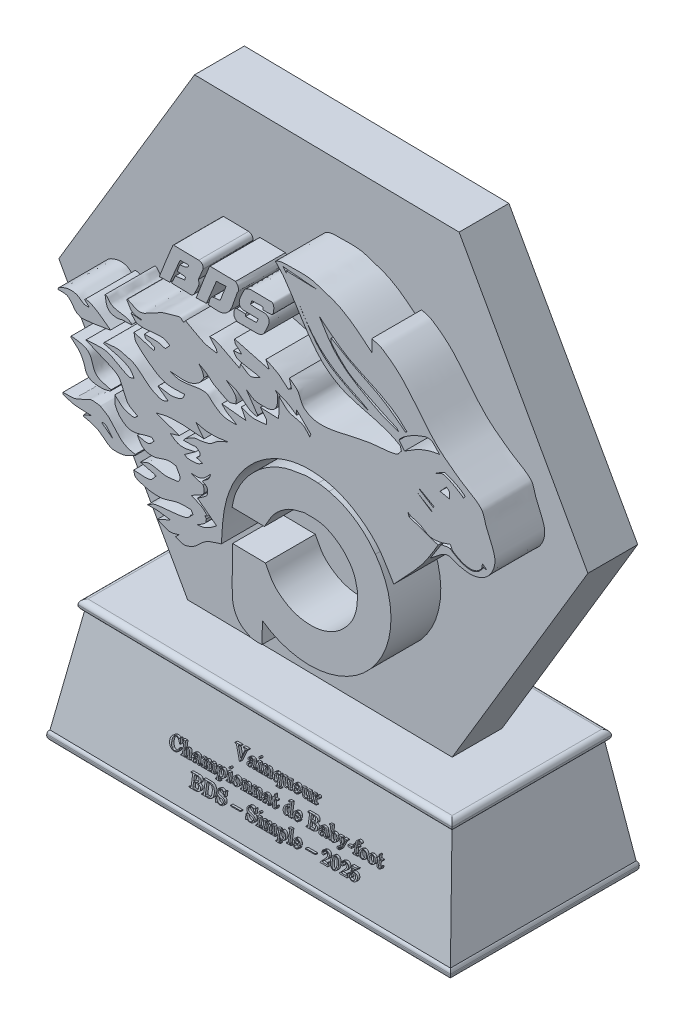
SolidWorks part; units mm, degrees
ref_plane "Plan de face" through (0, 0, 0) normal (0, 0, 1) x (1, 0, 0)
ref_plane "Plan de dessus" through (0, 0, 0) normal (0, 1, 0) x (1, 0, 0)
ref_plane "Plan de droite" through (0, 0, 0) normal (1, 0, 0) x (0, 0, -1)
sketch "Esquisse3" plane through (0, 0, 0) normal (0, 0, 1) x (1, 0, 0)
  line L0 (336.1667, 1024) -> (1680.8333, 1024) construction
  line L1 (1302, 1687) -> (1302, 1736)
  line L2 (1537, 1090) -> (1581, 1159)
  line L3 (1445.599, 1206.4377) -> (1452, 1191)
  line L4 (1452, 1191) -> (1568, 1151)
  line L5 (514, 653) -> (528, 667)
  line L6 (441, 677) -> (494, 701)
  line L7 (584, 764) -> (577, 778)
  line L8 (437, 826) -> (373, 842)
  line L9 (484, 1110) -> (443, 1141)
  line L10 (347, 1280) -> (428, 1256)
  line L11 (428, 1256) -> (430, 1269)
  line L12 (473, 1286) -> (491, 1306)
  line L13 (335, 1341) -> (376, 1337)
  line L14 (376, 1337) -> (378, 1339)
  line L15 (318, 1380) -> (321, 1382)
  line L16 (546, 1414) -> (554, 1424)
  line L17 (771, 1367) -> (775, 1384)
  line L18 (746, 1416) -> (780, 1420)
  line L19 (751, 1459) -> (890, 1422)
  line L20 (890, 1422) -> (877, 1451)
  line L21 (967, 1392) -> (980, 1399)
  line L22 (980, 1399) -> (971, 1433)
  line L23 (945, 1808) -> (1083, 1796)
  line L24 (1083, 1796) -> (959, 1800)
  line L25 (959, 1800) -> (958, 1794)
  line L26 (958, 1794) -> (960, 1791)
  line L27 (960, 1791) -> (945, 1808)
  line L28 (1444, 1481) -> (1437, 1478)
  line L29 (1433, 1410) -> (1411, 1437)
  line L30 (1677, 1373) -> (1670, 1365)
  line L31 (1613, 1334) -> (1576, 1342)
  line L32 (1601, 1369) -> (1576, 1342)
  line L33 (1000, 1318) -> (999, 1338)
  line L34 (999, 1338) -> (1057, 1281)
  line L35 (1057, 1281) -> (1053, 1269)
  line L36 (930, 1348) -> (928, 1270)
  line L37 (928, 1270) -> (855, 1273)
  line L38 (778, 1236) -> (797, 1198)
  line L39 (840, 1234) -> (844, 1240)
  line L40 (844, 1240) -> (799, 1306)
  line L41 (1654, 1326) -> (1658, 1324)
  line L42 (1658, 1324) -> (1654, 1325)
  line L43 (1654, 1326) -> (1654, 1325)
  line L44 (1551, 1277) -> (1494, 1309)
  line L45 (1551, 1277) -> (1549, 1272)
  line L46 (1549, 1272) -> (1493, 1307)
  line L47 (1493, 1307) -> (1494, 1309)
  line L48 (1483, 1293) -> (1544, 1256)
  line L49 (1542, 1254) -> (1544, 1256)
  line L50 (1542, 1254) -> (1483, 1293)
  line L51 (1746, 1175) -> (1763, 1163)
  line L52 (1763, 1163) -> (1760, 1162)
  line L53 (1760, 1162) -> (1750.0098, 1163.665)
  line L55 (1743, 1157) -> (1746, 1175)
  line L56 (598, 970) -> (623, 963)
  line L57 (550, 957) -> (594, 988)
  line L58 (493, 1001) -> (529, 1012)
  line L59 (529, 1012) -> (437, 1044)
  line L60 (595, 1092) -> (628, 1050)
  line L61 (602, 831) -> (679, 773)
  line L62 (638, 777) -> (631, 785)
  line L63 (631, 785) -> (643, 789)
  line L64 (574, 905) -> (625, 888)
  line L65 (232, 1354) -> (231, 1353)
  line L66 (168, 1277) -> (149, 1295)
  line L67 (153, 1299) -> (149, 1295)
  line L68 (255, 1034) -> (253, 1029)
  line L69 (95, 1141) -> (94, 1136)
  line L70 (352, 858) -> (352, 854)
  line L71 (144, 891) -> (144, 887)
  line L72 (144, 891) -> (174, 905)
  line L73 (62, 923) -> (62, 929)
  line L74 (1234, 1501) -> (1241.5869, 1497.8498)
  line L75 (678, 1623) -> (717, 1625)
  line L76 (862.8036, 535.7693) -> (861, 451)
  line L77 (743, 744) -> (875, 742)
  line L78 (871, 867) -> (741, 869)
  line L79 (865, 1617) -> (864, 1628)
  line L80 (821, 1627) -> (864, 1628)
  line L81 (821, 1627) -> (814, 1611)
  line L82 (794, 1568) -> (795, 1559)
  line L83 (795, 1559) -> (839, 1560)
  line L84 (839, 1560) -> (846, 1576)
  line L85 (693, 1564) -> (717, 1625)
  line L86 (700, 1208) -> (797, 1198)
  line L87 (678, 1623) -> (638, 1526)
  line L88 (638, 1526) -> (597, 1525)
  line L89 (498, 1527) -> (513, 1559)
  line L90 (513, 1559) -> (551, 1564)
  line L91 (551, 1564) -> (554, 1576)
  line L92 (554, 1576) -> (521, 1580)
  line L93 (521, 1580) -> (531, 1607)
  line L94 (567, 1620) -> (565, 1624)
  line L95 (565, 1624) -> (532, 1623)
  line L96 (532, 1623) -> (491, 1526)
  line L97 (491, 1526) -> (449, 1525)
  line L98 (624.8796, 1638.9367) -> (605.4226, 1592.9044)
  line L99 (604.6984, 1566.7534) -> (589.7477, 1536.2154)
  line L100 (573.9653, 1525) -> (498, 1527)
  line L101 (264.0246, 866.4916) -> (217, 902)
  arc A0 (607, 1661) -> (624.8796, 1638.9367) centre (606.6207, 1642.4164) cw
  arc A1 (605.4226, 1592.9044) -> (604.6984, 1566.7534) centre (576.3678, 1580.6235) cw
  arc A2 (589.7477, 1536.2154) -> (573.9653, 1525) centre (571.5353, 1545.1319) cw
  arc A3 (862.8036, 535.7693) -> (1316.5669, 993.1753) centre (1052.5129, 801.3486) ccw
  arc A4 (1129.8066, 1118.4411) -> (1086.8314, 1125.9164) centre (1052.5129, 801.3486) ccw
  spline S0 degree 3 poles (915, 1811) (920.6667, 1813.6667) (925.9164, 1817.5129) (932, 1819) (941.1183, 1821.2289) (950.6154, 1822.1997) (960, 1822) (1000.4122, 1821.1402) (1042.9169, 1827.5488) (1081, 1814) (1113.09, 1802.5833) (1146.9207, 1794.9796) (1177, 1779) (1222.6884, 1754.728) (1262.8151, 1720.7801) (1302, 1687) knots 0 0 0 0 1 1 1 2 2 2 3 3 3 4 4 4 5 5 5 5
  spline S1 degree 3 poles (1302, 1736) (1317, 1730.3333) (1333.5756, 1727.7691) (1347, 1719) (1375.3732, 1700.4659) (1402.4901, 1679.4098) (1426, 1655) (1472.4253, 1606.7976) (1509.2053, 1549.8439) (1556, 1502) (1583.8463, 1473.5293) (1617.0572, 1450.7835) (1649, 1427) (1678.4402, 1405.0798) (1714.1626, 1391.0701) (1740, 1365) (1752.6359, 1352.2503) (1753.5167, 1331.7388) (1760, 1315) (1771.8506, 1284.4039) (1788.3447, 1255.1289) (1795, 1223) (1798.2706, 1207.2107) (1795.1053, 1189.924) (1789, 1175) (1782.6895, 1159.5742) (1772.3333, 1145) (1759, 1135) (1744.6396, 1124.2297) (1726.7988, 1117.3288) (1709, 1115) (1690.0565, 1112.5214) (1670.8107, 1117.6598) (1652, 1121) (1635.0445, 1124.0108) (1618.6273, 1138.4821) (1602, 1134) (1576.7377, 1127.1902) (1558.6667, 1104.6667) (1537, 1090) knots 0 0 0 0 1 1 1 2 2 2 3 3 3 4 4 4 5 5 5 6 6 6 7 7 7 8 8 8 9 9 9 10 10 10 11 11 11 12 12 12 13 13 13 13
  spline S2 degree 3 poles (1581, 1159) (1592.9734, 1159.921) (1605.2835, 1164.5242) (1617, 1162.6354) knots 0 0 0 0 0.921032 0.921032 0.921032 0.921032
  spline S3 degree 3 poles (1626.6587, 1159.5467) (1622.8097, 1165.1023) (1620.6123, 1172.2204) (1617, 1178) knots 2.277549 2.277549 2.277549 2.277549 3 3 3 3
  spline S4 degree 3 poles (1617, 1178) (1603, 1173.6667) (1589.4463, 1167.4664) (1575, 1165) (1561.8527, 1162.7553) (1547.9107, 1160.6528) (1535, 1164) (1519.9865, 1167.8924) (1508.1253, 1179.5944) (1494, 1186) (1479.3968, 1192.6224) (1461.6455, 1193.1408) (1449, 1203) (1447.7012, 1204.0126) (1446.5813, 1205.1696) (1445.599, 1206.4377) knots 0 0 0 0 1 1 1 2 2 2 3 3 3 4 4 4 4.153424 4.153424 4.153424 4.153424
  spline S5 degree 3 poles (1568, 1151) (1562.6667, 1142) (1557.7044, 1132.7695) (1552, 1124) (1535.3644, 1098.4259) (1520.3192, 1071.6124) (1501, 1048) (1466.1847, 1005.448) (1427, 966.6667) (1390, 926) knots 0 0 0 0 1 1 1 2 2 2 3 3 3 3
  spline S6 degree 3 poles (1390, 926) (1370, 957.3333) (1353.6926, 991.3567) (1330, 1020) (1308.6483, 1045.8133) (1283.3166, 1068.6086) (1256, 1088) (1228.8829, 1107.2498) (1199.2278, 1123.5669) (1168, 1135) (1137.6118, 1146.1257) (1105.2971, 1152.9709) (1073, 1155) (1040.9523, 1157.0135) (1008.2798, 1154.2583) (977, 1147) (947.2739, 1140.1022) (918.485, 1128.1581) (892, 1113) (864.9769, 1097.534) (839.9344, 1078.0981) (818, 1056) (794.8916, 1032.7191) (774.5075, 1006.3461) (758, 978) (741.238, 949.2167) (728.0873, 918.0447) (719, 886) (703.7834, 832.3415) (700.9314, 775.6973) (698, 720) knots 0 0 0 0 1 1 1 2 2 2 3 3 3 4 4 4 5 5 5 6 6 6 7 7 7 8 8 8 9 9 9 10 10 10 10
  spline S7 degree 3 poles (698, 720) (678, 712.6667) (656.4567, 708.6361) (638, 698) (616.6203, 685.6795) (602.0285, 663.1191) (580, 652) (548.5317, 636.116) (537.3019, 642.1258) (514, 653) knots 0 0 0 0 1 1 1 2 2 2 3 3 3 3
  spline S8 degree 3 poles (528, 667) (525.4489, 666.4898) (497.27, 654.9179) (484, 660) (469.6066, 665.5124) (455.3333, 671.3333) (441, 677) knots 0 0 0 0 1 1 1 2 2 2 2
  spline S9 degree 3 poles (494, 701) (477, 703.3333) (460.1099, 706.6982) (443, 708) (429.3727, 709.0369) (415.6667, 708) (402, 708) knots 0 0 0 0 1 1 1 2 2 2 2
  spline S10 degree 3 poles (402, 708) (412, 713.3333) (420.9098, 721.6652) (432, 724) (472.1351, 732.4495) (514.3355, 729.562) (554, 740) (566.3846, 743.2591) (574, 756) (584, 764) knots 0 0 0 0 1 1 1 2 2 2 3 3 3 3
  spline S11 degree 3 poles (577, 778) (560, 777.6667) (542.804, 779.5957) (526, 777) (501.5513, 773.2234) (478.6767, 760.7501) (454, 759) (430.9039, 757.362) (407.166, 760.3084) (385, 767) (348.0895, 778.1428) (350.2029, 779.9856) (346, 801) knots 0 0 0 0 1 1 1 2 2 2 3 3 3 4 4 4 4
  spline S12 degree 3 poles (346, 801) (367.6667, 801) (390.1074, 795.2603) (411, 801) (422.5936, 804.185) (428.3333, 817.6667) (437, 826) knots 0 0 0 0 1 1 1 2 2 2 2
  spline S13 degree 3 poles (373, 842) (385, 846.3333) (396.25, 854.5364) (409, 855) (435.1955, 855.9526) (460.8999, 842.5721) (487, 845) (500.0501, 846.214) (513, 848.3333) (526, 850) knots 0 0 0 0 1 1 1 2 2 2 3 3 3 3
  spline S14 degree 3 poles (526, 850) (528, 856.3333) (533.3025, 862.4874) (532, 869) (529.7195, 880.4027) (521.3333, 889.6667) (516, 900) knots 0 0 0 0 1 1 1 2 2 2 2
  spline S15 degree 3 poles (516, 900) (505.3333, 901) (494.6103, 904.4832) (484, 903) (463.1813, 900.0899) (443.9834, 888.259) (423, 887) (409.6035, 886.1962) (395.1111, 889.4731) (384, 897) (373.1244, 904.3673) (368.6667, 918.3333) (361, 929) knots 0 0 0 0 1 1 1 2 2 2 3 3 3 4 4 4 4
  spline S16 degree 3 poles (361, 929) (376, 927) (391.1443, 920.1176) (406, 923) (415.5122, 924.8457) (420.6667, 935.6667) (428, 942) knots 0 0 0 0 1 1 1 2 2 2 2
  spline S17 degree 3 poles (428, 942) (424, 944.6667) (420.7819, 950.4947) (416, 950) (390.5019, 947.3623) (366.6332, 933.2229) (341, 933) (326.6401, 932.8751) (312.2458, 940.0695) (301, 949) (288.6786, 958.7846) (279.0102, 972.4593) (273, 987) (268.2733, 998.4355) (271, 1011.6667) (270, 1024) knots 0 0 0 0 1 1 1 2 2 2 3 3 3 4 4 4 5 5 5 5
  spline S18 degree 3 poles (270, 1024) (283.6667, 1013.6667) (294.8981, 998.8552) (311, 993) (347.6119, 979.6866) (348.3963, 982.3963) (362, 996) knots 0 0 0 0 1 1 1 2 2 2 2
  spline S19 degree 3 poles (362, 996) (349.3333, 1004) (334.0691, 1008.9069) (324, 1020) (313.6798, 1031.3697) (310.3408, 1047.5133) (303, 1061) (296.0028, 1073.8554) (292.6952, 1090.1997) (281, 1099) (257.6507, 1116.5698) (228.5806, 1124.8608) (202, 1137) (186.2331, 1144.2006) (170, 1150.3333) (154, 1157) knots 0 0 0 0 1 1 1 2 2 2 3 3 3 4 4 4 5 5 5 5
  spline S20 degree 3 poles (154, 1157) (155.3333, 1157.3333) (156.6257, 1157.9838) (158, 1158) (184.9981, 1158.3176) (212.8154, 1164.5853) (239, 1158) (269.9392, 1150.2189) (294.8755, 1126.5021) (325, 1116) (332.348, 1113.4383) (340.3333, 1118.6667) (348, 1120) knots 0 0 0 0 1 1 1 2 2 2 3 3 3 4 4 4 4
  spline S21 degree 3 poles (348, 1120) (341.6667, 1128.6667) (337.8909, 1139.9855) (329, 1146) (298.4419, 1166.6716) (259.637, 1171.4544) (224, 1181) knots 0 0 0 0 1 1 1 2 2 2 2
  spline S22 degree 3 poles (224, 1181) (226, 1182.6667) (227.4051, 1185.7896) (230, 1186) (253.9215, 1187.9396) (279.1881, 1193.4577) (302, 1186) (318.0306, 1180.7592) (335.4753, 1178.5719) (350, 1170) (376.6403, 1154.2779) (396.4202, 1128.0088) (424, 1114) (459.6438, 1095.8952) (463.5958, 1099.7979) (484, 1110) knots 0 0 0 0 1 1 1 2 2 2 3 3 3 4 4 4 5 5 5 5
  spline S23 degree 3 poles (443, 1141) (448.6949, 1142.8983) (443.1637, 1141.6511) (450, 1141) (469.6483, 1139.1287) (489.5876, 1132.4345) (509, 1136) (542.4065, 1142.1359) (543.3635, 1148.1815) (551, 1166) knots 0 0 0 0 1 1 1 2 2 2 3 3 3 3
  spline S24 degree 3 poles (551, 1166) (526.3333, 1166.3333) (501.1599, 1162.0146) (477, 1167) (458.1643, 1170.8867) (440.8598, 1181.1209) (425, 1192) (400.2227, 1208.996) (375.9299, 1227.515) (356, 1250) (349.0749, 1257.813) (350, 1270) (347, 1280) knots 0 0 0 0 1 1 1 2 2 2 3 3 3 4 4 4 4
  spline S25 degree 3 poles (430, 1269) (388.8184, 1289.0628) (394.9727, 1274.0957) (389, 1295) knots 0 0 0 0 1 1 1 1
  spline S26 degree 3 poles (389, 1295) (407, 1294.6667) (425.0994, 1295.9179) (443, 1294) (453.2906, 1292.8974) (463, 1288.6667) (473, 1286) knots 0 0 0 0 1 1 1 2 2 2 2
  spline S27 degree 3 poles (491, 1306) (482, 1310.3333) (473.9581, 1318.2159) (464, 1319) (430.7546, 1321.6178) (396.8737, 1310.3936) (364, 1316) (351.4189, 1318.1456) (344.6667, 1332.6667) (335, 1341) knots 0 0 0 0 1 1 1 2 2 2 3 3 3 3
  spline S28 degree 3 poles (378, 1339) (365.6667, 1341.6667) (351.4183, 1339.8809) (341, 1347) (329.9297, 1354.5647) (325.6667, 1369) (318, 1380) knots 0 0 0 0 1 1 1 2 2 2 2
  spline S29 degree 3 poles (321, 1382) (337.6667, 1375.6667) (353.1715, 1362.8181) (371, 1363) (388.3324, 1363.1769) (403.2308, 1375.8044) (419, 1383) (437.5803, 1391.4784) (454.2051, 1404.9727) (474, 1410) (535.009, 1425.4944) (528.4316, 1431.5684) (546, 1414) knots 0 0 0 0 1 1 1 2 2 2 3 3 3 4 4 4 4
  spline S30 degree 3 poles (554, 1424) (579.3333, 1410.6667) (603.3907, 1394.5593) (630, 1384) (645.7983, 1377.7308) (663.3333, 1377.3333) (680, 1374) knots 0 0 0 0 1 1 1 2 2 2 2
  spline S31 degree 3 poles (680, 1374) (679.3333, 1378) (680.2674, 1382.638) (678, 1386) (670.338, 1397.3609) (660, 1406.6667) (651, 1417) knots 0 0 0 0 1 1 1 2 2 2 2
  spline S32 degree 3 poles (651, 1417) (660, 1416) (669.6412, 1417.4828) (678, 1414) (710.0621, 1400.6408) (740, 1382.6667) (771, 1367) knots 0 0 0 0 1 1 1 2 2 2 2
  spline S33 degree 3 poles (775, 1384) (791.3079, 1376.2006) (808.3586, 1355.94) (825, 1363) (834.7522, 1367.1373) (844.3333, 1371.6667) (854, 1376) knots 0 0 0 0 1 1 1 2 2 2 2
  spline S34 degree 3 poles (854, 1376) (846, 1378) (838.054, 1380.2299) (830, 1382) (807.7162, 1386.8975) (784.1489, 1387.4397) (763, 1396) (754.8896, 1399.2828) (751.6667, 1409.3333) (746, 1416) knots 0 0 0 0 1 1 1 2 2 2 3 3 3 3
  spline S35 degree 3 poles (780, 1420) (749.6731, 1451.41) (753.337, 1435.6296) (751, 1459) knots 0 0 0 0 1 1 1 1
  spline S36 degree 3 poles (877, 1451) (893.6667, 1442.3333) (911.2896, 1435.2991) (927, 1425) (941.4558, 1415.5234) (953.6667, 1403) (967, 1392) knots 0 0 0 0 1 1 1 2 2 2 2
  spline S37 degree 3 poles (971, 1433) (982, 1424) (995.2325, 1417.1862) (1004, 1406) (1014.9466, 1392.0336) (1015.9477, 1371.0219) (1029, 1359) (1042.717, 1346.3659) (1061.5274, 1338.5577) (1080, 1336) (1108.8188, 1332.0097) (1138.5521, 1336.904) (1167, 1343) (1206.3139, 1351.4244) (1245.3733, 1361.1971) (1285, 1368) (1323.1007, 1374.5409) (1362.6291, 1373.1077) (1400, 1383) (1409.5699, 1385.5332) (1414, 1397) (1421, 1404) knots 0 0 0 0 1 1 1 2 2 2 3 3 3 4 4 4 5 5 5 6 6 6 7 7 7 7
  spline S38 degree 3 poles (1421, 1404) (1418.3333, 1410) (1418.5514, 1418.4939) (1413, 1422) (1392.0534, 1435.2294) (1368.4815, 1444.1007) (1345, 1452) (1296.0045, 1468.4823) (1244.0544, 1475.9476) (1196, 1495) (1167.7816, 1506.1879) (1141.5168, 1522.8061) (1118, 1542) (1095.6955, 1560.2044) (1076.9818, 1582.7512) (1060, 1606) (1020.8468, 1659.6027) (988.3318, 1717.8068) (950, 1772) (939.9132, 1786.2607) (926.6667, 1798) (915, 1811) knots 0 0 0 0 1 1 1 2 2 2 3 3 3 4 4 4 5 5 5 6 6 6 7 7 7 7
  spline S39 degree 3 poles (1234, 1501) (1233.3071, 1501.2746) (1232.6555, 1501.6452) (1232, 1502) (1204.3218, 1516.9788) (1175.736, 1530.3978) (1149, 1547) (1118.5402, 1565.9145) (1091.9951, 1591.6844) (1070, 1620) (1033.5835, 1666.8811) (1004.352, 1718.9828) (974, 1770) knots 5 5 5 5 6 6 6 7 7 7 8 8 8 9 9 9 9
  spline S40 degree 3 poles (974, 1770) (1009.2632, 1712.8836) (1040.7926, 1651.7205) (1088, 1604) (1103.129, 1588.7065) (1119.6469, 1574.7141) (1137, 1562) (1153.4175, 1549.9713) (1171.1465, 1539.7712) (1189, 1530) (1220.5161, 1512.7513) (1254.8005, 1500.4619) (1285, 1481) (1298.4541, 1472.3296) (1262.1817, 1489.0571) (1241.5869, 1497.8498) knots 0 0 0 0 1 1 1 2 2 2 3 3 3 4 4 4 4.876532 4.876532 4.876532 4.876532
  spline S41 degree 3 poles (1091, 1708) (1133.0564, 1673.7942) (1174.7177, 1637.6494) (1223, 1613) (1284.8912, 1581.4029) (1352.3155, 1557.8776) (1407, 1515) (1420.1811, 1504.6649) (1431.6667, 1492.3333) (1444, 1481) knots 0 0 0 0 1 1 1 2 2 2 3 3 3 3
  spline S42 degree 3 poles (1437, 1478) (1402.4117, 1505.2291) (1367.5024, 1532.6613) (1329, 1554) (1294.7083, 1573.005) (1258.5431, 1588.4558) (1224, 1607) (1195.1856, 1622.4688) (1167.3333, 1639.6667) (1139, 1656) knots 0 0 0 0 1 1 1 2 2 2 3 3 3 3
  spline S43 degree 3 poles (1139, 1656) (1139.3333, 1650.6667) (1136.7754, 1644.2611) (1140, 1640) (1156.078, 1618.7541) (1175.1654, 1599.7898) (1195, 1582) (1207.6652, 1570.6405) (1221.9981, 1561.0243) (1237, 1553) (1279.4612, 1530.2882) (1323.6737, 1511.0145) (1367, 1490) (1406.2609, 1470.9573) (1395.2349, 1482.5182) (1409, 1466) knots 0 0 0 0 1 1 1 2 2 2 3 3 3 4 4 4 5 5 5 5
  spline S44 degree 3 poles (1409, 1466) (1382.5166, 1475.5954) (1354.8689, 1482.7719) (1330, 1496) (1264.0429, 1531.0836) (1201.8033, 1560.9883) (1152, 1618) (1128.157, 1645.2939) (1110.3276, 1677.3424) (1091, 1708) knots 0 0 0 0 1 1 1 2 2 2 3 3 3 3
  spline S45 degree 3 poles (1411, 1437) (1422.7965, 1460.5929) (1479.2149, 1489.3274) (1503, 1497) (1509.6241, 1499.1368) (1516.0477, 1502.6689) (1523, 1503) (1528.3377, 1503.2542) (1533.6929, 1502.6244) (1539, 1502) (1546.2224, 1501.1503) (1568.8037, 1474.1963) (1574, 1469) knots 0 0 0 0 1 1 1 2 2 2 3 3 3 4 4 4 4
  spline S46 degree 3 poles (1574, 1469) (1515.6013, 1461.3828) (1480.7028, 1441.8019) (1433, 1410) knots 0 0 0 0 1 1 1 1
  spline S47 degree 3 poles (1556, 1394) (1558.3701, 1396.3701) (1590.3583, 1416) (1594, 1416) (1607.1855, 1416) (1667.2767, 1387.5849) (1677, 1373) knots 0 0 0 0 1 1 1 2 2 2 2
  spline S48 degree 3 poles (1670, 1365) (1657.2666, 1377.7334) (1604.6796, 1406.1748) (1589, 1407) (1577.874, 1407.5856) (1564.0025, 1397.8273) (1556, 1394) knots 0 0 0 0 1 1 1 2 2 2 2
  spline S49 degree 3 poles (1601, 1369) (1604.5506, 1366.1595) (1613.803, 1362.3203) (1614, 1357) (1614.284, 1349.3313) (1613.3333, 1341.6667) (1613, 1334) knots 0 0 0 0 1 1 1 2 2 2 2
  spline S50 degree 3 poles (914, 1363) (932, 1355.3333) (950.665, 1349.0706) (968, 1340) (979.4691, 1333.9987) (989.3333, 1325.3333) (1000, 1318) knots 0 0 0 0 1 1 1 2 2 2 2
  spline S51 degree 3 poles (1053, 1269) (1043.6667, 1278.3333) (1036.6084, 1290.7178) (1025, 1297) (1007.4766, 1306.4832) (985.5551, 1305.5757) (968, 1315) (953.219, 1322.9351) (942.6667, 1337) (930, 1348) knots 0 0 0 0 1 1 1 2 2 2 3 3 3 3
  spline S52 degree 3 poles (855, 1273) (882.3131, 1233.6692) (882.4018, 1251.411) (878, 1225) knots 0 0 0 0 1 1 1 1
  spline S53 degree 3 poles (878, 1225) (860.3333, 1223.6667) (842.6107, 1219.0628) (825, 1221) (808.6534, 1222.7981) (793.6667, 1231) (778, 1236) knots 0 0 0 0 1 1 1 2 2 2 2
  spline S54 degree 3 poles (700, 1208) (706.3333, 1201.6667) (711.7033, 1194.1943) (719, 1189) (731.5298, 1180.0804) (745.6667, 1173.6667) (759, 1166) knots 0 0 0 0 1 1 1 2 2 2 2
  spline S55 degree 3 poles (759, 1166) (757, 1165.3333) (755.1067, 1163.922) (753, 1164) (736.9555, 1164.5942) (720.3884, 1163.4201) (705, 1168) (691.6848, 1171.9629) (680.5843, 1181.3316) (669, 1189) (656.8812, 1197.0223) (648.4052, 1213.0732) (634, 1215) (592.68, 1220.5269) (547.8534, 1195.8903) (509, 1211) (503.981, 1212.9518) (499, 1215) (494, 1217) knots 0 0 0 0 1 1 1 2 2 2 3 3 3 4 4 4 5 5 5 6 6 6 6
  spline S56 degree 3 poles (494, 1217) (517.3333, 1216.3333) (540.9428, 1211.3594) (564, 1215) (579.9136, 1217.5127) (595.0147, 1225.4639) (608, 1235) (617.0274, 1241.6295) (621.3333, 1253) (628, 1262) knots 0 0 0 0 1 1 1 2 2 2 3 3 3 3
  spline S57 degree 3 poles (628, 1262) (625.6667, 1269.3333) (624.5116, 1277.1523) (621, 1284) (617.7448, 1290.3476) (612.3333, 1295.3333) (608, 1301) knots 0 0 0 0 1 1 1 2 2 2 2
  spline S58 degree 3 poles (608, 1301) (617.3333, 1295.6667) (627.138, 1291.0844) (636, 1285) (649.5212, 1275.7168) (660.3578, 1262.3895) (675, 1255) (734.878, 1224.7812) (723.0011, 1223.8575) (757, 1236) knots 0 0 0 0 1 1 1 2 2 2 3 3 3 3
  spline S59 degree 3 poles (757, 1236) (756.6667, 1244.3333) (759.5511, 1253.4538) (756, 1261) (748.0708, 1277.8495) (730.7925, 1288.6881) (716, 1300) knots 0 0 0 0 1 1 1 2 2 2 2
  spline S60 degree 3 poles (716, 1300) (730, 1294.6667) (745.1306, 1291.6696) (758, 1284) (778.4448, 1271.8157) (794.6796, 1253.3905) (815, 1241) (822.3886, 1236.4947) (831.6667, 1236.3333) (840, 1234) knots 0 0 0 0 1 1 1 2 2 2 3 3 3 3
  spline S61 degree 3 poles (799, 1306) (810.3333, 1299.3333) (820.288, 1289.3606) (833, 1286) (850.1072, 1281.4774) (868.3163, 1283.6316) (886, 1283) (887.0534, 1282.9624) (888.0572, 1283.5286) (889, 1284) (896.7345, 1287.8672) (906.3175, 1289.4818) (912, 1296) (918.3862, 1303.3254) (922.4031, 1313.3001) (923, 1323) (924.841, 1352.9155) (924.4477, 1352.5523) (914, 1363) knots 0 0 0 0 1 1 1 2 2 2 3 3 3 4 4 4 5 5 5 6 6 6 6
  spline S62 degree 3 poles (595, 1092) (609.6667, 1088.6667) (624.0211, 1083.3617) (639, 1082) (675.9728, 1078.6388) (692.3078, 1083.4907) (725, 1088) knots 0 0 0 0 1 1 1 2 2 2 2
  spline S63 degree 3 poles (725, 1088) (711.5274, 1081.2637) (696.9722, 1076.6557) (684, 1069) (673.3204, 1062.6973) (664.9736, 1052.7756) (654, 1047) (645.6935, 1042.6282) (636.1763, 1040.9764) (627, 1039) (602.8772, 1033.8043) (599.6204, 1038.6814) (587, 1032) (576.3252, 1026.3486) (565.0499, 1021.6999) (555, 1015) (550.8769, 1012.2513) (548.3333, 1007.6667) (545, 1004) knots 0 0 0 0 1 1 1 2 2 2 3 3 3 4 4 4 5 5 5 6 6 6 6
  spline S64 degree 3 poles (545, 1004) (600.4214, 1002.0889) (592.1008, 1015.5116) (613, 992) knots 0 0 0 0 1 1 1 1
  spline S65 degree 3 poles (613, 992) (612.3333, 988.6667) (612.915, 984.8086) (611, 982) (607.6779, 977.1275) (602.3333, 974) (598, 970) knots 0 0 0 0 1 1 1 2 2 2 2
  spline S66 degree 3 poles (623, 963) (617.6667, 959.6667) (612.9666, 954.9889) (607, 953) (598.6813, 950.2271) (589.7671, 948.8346) (581, 949) (558.8759, 949.4174) (560.1362, 949.3979) (550, 957) knots 0 0 0 0 1 1 1 2 2 2 3 3 3 3
  spline S67 degree 3 poles (594, 988) (578, 985) (562.2776, 979.201) (546, 979) (520.046, 978.6796) (511.1814, 987.869) (493, 1001) knots 0 0 0 0 1 1 1 2 2 2 2
  spline S68 degree 3 poles (437, 1044) (438.3333, 1044.6667) (439.5424, 1045.6877) (441, 1046) (458.2591, 1049.6984) (475.4011, 1054.6462) (493, 1056) (519.5902, 1058.0454) (546.4778, 1057.7918) (573, 1055) (591.3078, 1053.0729) (609.6667, 1051.6667) (628, 1050) knots 0 0 0 0 1 1 1 2 2 2 3 3 3 4 4 4 4
  spline S69 degree 3 poles (655, 941) (652.6667, 934.6667) (652.1823, 927.2976) (648, 922) (641.8381, 914.1949) (632.3071, 909.745) (625, 903) (623.5718, 901.6817) (623, 899.6667) (622, 898) knots 0 0 0 0 1 1 1 2 2 2 3 3 3 3
  spline S70 degree 3 poles (622, 898) (627.7349, 895.1326) (635.2169, 894.1768) (639, 889) (644.2386, 881.8315) (644.3408, 863.1311) (637, 856) (626.7162, 846.01) (613.1955, 839.9564) (602, 831) knots 0 0 0 0 1 1 1 2 2 2 3 3 3 3
  spline S71 degree 3 poles (679, 773) (653.2815, 754.2956) (635.6045, 739) (603, 739) knots 0 0 0 0 1 1 1 1
  spline S72 degree 3 poles (603, 739) (613, 746) (624.7304, 751.0215) (633, 760) (637.0016, 764.3446) (636.3333, 771.3333) (638, 777) knots 0 0 0 0 1 1 1 2 2 2 2
  spline S73 degree 3 poles (643, 789) (635.3333, 795.6667) (628.6155, 803.6153) (620, 809) (606.7117, 817.3052) (591.5494, 822.1802) (577, 828) knots 0 0 0 0 1 1 1 2 2 2 2
  spline S74 degree 3 poles (577, 828) (616.4664, 852.9685) (638.0843, 848.747) (625, 888) knots 0 0 0 0 1 1 1 1
  spline S75 degree 3 poles (574, 905) (587.3333, 905.6667) (601.3163, 902.8352) (614, 907) (630.8684, 912.5389) (642.4457, 928.4457) (655, 941) knots 0 0 0 0 1 1 1 2 2 2 2
  spline S76 degree 3 poles (232, 1354) (242.4415, 1351.9117) (248.1212, 1335.3194) (258, 1330) (283.5429, 1316.2461) (317.1934, 1324.8066) (339, 1303) knots 0 0 0 0 1 1 1 2 2 2 2
  spline S77 degree 3 poles (339, 1303) (338.3333, 1302.3333) (337.9399, 1301.0742) (337, 1301) (325.0326, 1300.0552) (312.9871, 1300.648) (301, 1300) (296.7122, 1299.7682) (287.0907, 1296) (283, 1296) (239.2897, 1296) (236.3377, 1315.6359) (231, 1353) knots 0 0 0 0 1 1 1 2 2 2 3 3 3 4 4 4 4
  spline S78 degree 3 poles (42, 1277) (43, 1279.3333) (42.9398, 1282.5167) (45, 1284) (51.6537, 1288.7907) (59.2562, 1292.3065) (67, 1295) (74.7182, 1297.6846) (82.8298, 1299.8398) (91, 1300) (100.0965, 1300.1784) (109.5318, 1299.3268) (118, 1296) (128.5895, 1291.8398) (136.3646, 1282.0414) (147, 1278) (153.5509, 1275.5107) (161, 1277.3333) (168, 1277) knots 0 0 0 0 1 1 1 2 2 2 3 3 3 4 4 4 5 5 5 6 6 6 6
  spline S79 degree 3 poles (153, 1299) (192.7282, 1291.9891) (220.1759, 1262.8827) (253, 1241) knots 0 0 0 0 1 1 1 1
  spline S80 degree 3 poles (253, 1241) (252.3333, 1240.6667) (251.7352, 1240.1225) (251, 1240) (210.5395, 1233.2566) (176.8812, 1226.7192) (137, 1224) (136.2564, 1223.9493) (135.673, 1224.6795) (135, 1225) (128.6728, 1228.0129) (121.209, 1229.3119) (116, 1234) (104.2292, 1244.5937) (97.4114, 1260.1646) (85, 1270) (73.6184, 1279.0194) (56.5056, 1276.3093) (42, 1277) knots 0 0 0 0 1 1 1 2 2 2 3 3 3 4 4 4 5 5 5 6 6 6 6
  spline S81 degree 3 poles (95, 1141) (114.8476, 1138.9108) (147.1123, 1136.4433) (163, 1122) (187.4478, 1099.7747) (173.8492, 1057.8926) (219, 1044) (219.3388, 1043.8958) (245.2794, 1035.9441) (255, 1034) knots 0 0 0 0 1 1 1 2 2 2 3 3 3 3
  spline S82 degree 3 poles (253, 1029) (243.9623, 1025.9874) (234.6235, 1022.6637) (225, 1022) (203.027, 1020.4846) (168.7372, 1020.6485) (156, 1044) (151.1278, 1052.9324) (149.628, 1063.5673) (146, 1073) (142.3376, 1082.5223) (136.6973, 1092.4541) (131, 1101) (121.2159, 1115.6762) (106.0916, 1123.9084) (94, 1136) knots 0 0 0 0 1 1 1 2 2 2 3 3 3 4 4 4 5 5 5 5
  spline S83 degree 3 poles (62, 929) (77.3333, 929.3333) (92.6763, 929.3615) (108, 930) (108.7447, 930.031) (109.3133, 930.7101) (110, 931) (124.3148, 937.044) (138.77, 942.7588) (153, 949) (161.8999, 952.9034) (170.2844, 959.7741) (180, 960) (190.0472, 960.2337) (200.0277, 958.2465) (210, 957) (210.7396, 956.9075) (211.3659, 956.3917) (212, 956) (222.7019, 949.39) (234.3976, 944.1251) (244, 936) (256.2407, 925.6425) (265.9722, 912.6404) (277, 901) (283.9723, 893.6403) (289.9517, 885.1646) (298, 879) (305.8143, 873.0146) (314.8261, 868.5676) (324, 865) (332.9664, 861.5131) (342.6667, 860.3333) (352, 858) knots 0 0 0 0 1 1 1 2 2 2 3 3 3 4 4 4 5 5 5 6 6 6 7 7 7 8 8 8 9 9 9 10 10 10 11 11 11 11
  spline S84 degree 3 poles (352, 854) (338.6667, 847.6667) (326.0036, 839.6679) (312, 835) (301.7579, 831.586) (290.7946, 830.1799) (280, 830) (270.5732, 829.8429) (260.4327, 829.7836) (252, 834) (233.8035, 843.0982) (219.813, 859.1721) (202, 869) (184.2757, 878.7789) (163.6925, 882.3113) (144, 887) knots 0 0 0 0 1 1 1 2 2 2 3 3 3 4 4 4 5 5 5 5
  spline S85 degree 3 poles (174, 905) (144.9735, 907.7319) (114.3398, 903.8741) (87, 914) (78.6945, 917.0761) (70.3333, 920) (62, 923) knots 0 0 0 0 1 1 1 2 2 2 2
  spline S86 degree 3 poles (217, 902) (237.2594, 912.1297) (250.3229, 878.0008) (264.0246, 866.4916) knots 0 0 0 0 0.954263 0.954263 0.954263 0.954263
  spline S87 degree 3 poles (741, 869) (745.6667, 887.3333) (747.7541, 906.5247) (755, 924) (764.8836, 947.837) (777.0331, 970.9791) (792, 992) (806.9169, 1012.9507) (824.8476, 1031.8352) (844, 1049) (860.3907, 1063.6898) (878.7758, 1076.2821) (898, 1087) (916.6558, 1097.401) (936.5111, 1105.9645) (957, 1112) (979.7651, 1118.706) (1003.646, 1120.7794) (1027, 1125) (1031.3144, 1125.7797) (1035.6196, 1127.1844) (1040, 1127) (1063.1964, 1126.0233) (1077.3953, 1125.9069) (1086.8314, 1125.9164) knots 0 0 0 0 1 1 1 2 2 2 3 3 3 4 4 4 5 5 5 6 6 6 7 7 7 7.312652 7.312652 7.312652 7.312652
  spline S88 degree 3 poles (1129.8066, 1118.4411) (1149.3282, 1112.2707) (1169.4776, 1107.6732) (1188, 1099) (1210.21, 1088.6001) (1231.5798, 1075.9766) (1251, 1061) (1276.9315, 1041.002) (1298.6831, 1018.304) (1316.5669, 993.1753) knots 8.076053 8.076053 8.076053 8.076053 9 9 9 10 10 10 10.407544 10.407544 10.407544 10.407544
  spline S89 degree 3 poles (861, 451) (860.7904, 451.0102) (822.8237, 449.1685) (811, 456) (798.6701, 463.124) (785.1535, 469.0158) (775, 479) (764.7166, 489.112) (756.2735, 501.5765) (751, 515) (745.0476, 530.1515) (742.5683, 546.7311) (742, 563) (739.8935, 623.2975) (742.6667, 683.6667) (743, 744) knots 0 0 0 0 1 1 1 2 2 2 3 3 3 4 4 4 5 5 5 5
  spline S90 degree 3 poles (875, 742) (886.3333, 722.6667) (894.6188, 701.1873) (909, 684) (922.3654, 668.0268) (939.2502, 654.8959) (957, 644) (973.3018, 633.993) (991.3781, 626.3721) (1010, 622) (1030.1849, 617.2609) (1051.3145, 615.5856) (1072, 617) (1090.7946, 618.2851) (1109.6347, 622.6968) (1127, 630) (1145.7608, 637.8901) (1163.6526, 648.6329) (1179, 662) (1195.0596, 675.9874) (1208.9898, 692.77) (1220, 711) (1229.601, 726.8968) (1236.1194, 744.8388) (1240, 763) (1244.5408, 784.251) (1243.7239, 806.3068) (1245, 828) (1245.0619, 829.0523) (1244.2849, 829.9851) (1244, 831) (1238.9512, 848.9864) (1237.0946, 868.1632) (1229, 885) (1220.1849, 903.3353) (1207.9538, 920.1953) (1194, 935) (1180.3243, 949.5096) (1164.2355, 961.9753) (1147, 972) (1131.2153, 981.1809) (1113.9175, 988.4777) (1096, 992) (1074.3909, 996.248) (1052.0135, 994.3619) (1030, 995) (1028.9463, 995.0305) (1028.0082, 994.3076) (1027, 994) (1008.3412, 988.3075) (988.4483, 985.7242) (971, 977) (952.6309, 967.8155) (935.7836, 955.2556) (921, 941) (899.5706, 920.3359) (885.381, 893.0655) (871, 867) knots 0 0 0 0 1 1 1 2 2 2 3 3 3 4 4 4 5 5 5 6 6 6 7 7 7 8 8 8 9 9 9 10 10 10 11 11 11 12 12 12 13 13 13 14 14 14 15 15 15 16 16 16 17 17 17 18 18 18 19 19 19 19
  spline S91 degree 3 poles (846, 1576) (825.6667, 1576.3333) (805.3255, 1576.3443) (785, 1577) (784.5288, 1577.0152) (784.4216, 1577.7892) (784, 1578) (781.0636, 1579.4682) (777.3214, 1579.6786) (775, 1582) (763.606, 1593.394) (773.1825, 1614.365) (779, 1626) (782.4673, 1632.9346) (785.5327, 1640.0654) (789, 1647) (794.1673, 1657.3346) (809.3479, 1662.8816) (820, 1663) (846.0005, 1663.2889) (872.0062, 1662.6581) (898, 1662) (913.4911, 1661.6078) (908.2556, 1631.6817) (905, 1623) (904.1724, 1620.7931) (902.3379, 1618.2997) (900, 1618) (888.4233, 1616.5158) (876.6667, 1617.3333) (865, 1617) knots 0 0 0 0 1 1 1 2 2 2 3 3 3 4 4 4 5 5 5 6 6 6 7 7 7 8 8 8 9 9 9 10 10 10 10
  spline S92 degree 3 poles (814, 1611) (834.3961, 1607.6007) (855.3353, 1609.7251) (876, 1609) (876.4711, 1608.9835) (876.5784, 1608.2108) (877, 1608) (900.3349, 1596.3325) (886.7947, 1573.5894) (878, 1556) (871.5364, 1543.0728) (872.5797, 1541.8957) (866, 1534) (861.0143, 1528.0171) (851.4293, 1524.2346) (844, 1524) (816.3471, 1523.1268) (788.6647, 1523.6707) (761, 1524) (760.5286, 1524.0056) (760.4093, 1524.7661) (760, 1525) (745.7347, 1533.1516) (744.2607, 1553.1129) (755, 1566) (756.4315, 1567.7178) (758.7669, 1568.8855) (761, 1569) (771.9906, 1569.5636) (783, 1568.3333) (794, 1568) knots 0 0 0 0 1 1 1 2 2 2 3 3 3 4 4 4 5 5 5 6 6 6 7 7 7 8 8 8 9 9 9 10 10 10 10
  spline S93 degree 3 poles (597, 1525) (614.6667, 1570) (631.5443, 1615.3178) (650, 1660) (650.6363, 1661.5404) (652.3334, 1662.9841) (654, 1663) (687.6717, 1663.3207) (721.3333, 1661.6667) (755, 1661) knots 0 0 0 0 1 1 1 2 2 2 3 3 3 3
  spline S94 degree 3 poles (755, 1661) (758.3333, 1656.6667) (763.712, 1653.3132) (765, 1648) (769.3984, 1629.8564) (765.2762, 1633.7036) (762, 1626) (745.1615, 1586.4069) (740.6004, 1525.4277) (688, 1523) (673.999, 1522.3538) (660, 1524.3333) (646, 1525) knots 0 0 0 0 1 1 1 2 2 2 3 3 3 4 4 4 4
  spline S95 degree 3 poles (646, 1525) (649.1605, 1534.4815) (649.9589, 1557.3414) (665, 1561) (674.1208, 1563.2186) (683.6667, 1563) (693, 1564) knots 0 0 0 0 1 1 1 2 2 2 2
  spline S96 degree 3 poles (449, 1525) (467, 1570) (483.6751, 1615.5528) (503, 1660) (503.8916, 1662.0506) (506.764, 1662.9785) (509, 1663) (541.672, 1663.3142) (574.3333, 1661.6667) (607, 1661) knots 0 0 0 0 1 1 1 2 2 2 3 3 3 3
  spline S97 degree 3 poles (531, 1607) (548.3042, 1610.708) (556.4301, 1605.9067) (567, 1620) knots 0 0 0 0 1 1 1 1
  spline S98 degree 3 poles (1626.6587, 1159.5467) (1661.3206, 1136.2747) (1712.7818, 1114.6388) (1743, 1157) knots 0 0 0 0 1 1 1 1
  spline S99 degree 3 poles (1617, 1162.6354) (1656.216, 1134.436) (1715.0222, 1104.1743) (1750.0098, 1163.665) knots 0 0 0 0 1 1 1 1
  point P209 (862.8036, 535.7693)
  point P210 (1316.5669, 993.1753)
extrude "Boss.-Extru.1" add sketch "Esquisse3" along normal blind 200
sketch "Esquisse4" plane through (0, 0, 0) normal (0, 0, -1) x (-1, 0, 0)
  line L0 (-875, 742) -> (-743, 744) construction
  line L1 (-390.38, 2097.2194) -> (-1452.38, 2081.1285)
  line L2 (-1452.38, 2081.1285) -> (-1969.4449, 1153.364)
  line L3 (-1969.4449, 1153.364) -> (-1424.5097, 241.6905)
  line L4 (-1424.5097, 241.6905) -> (-362.5097, 257.7814)
  line L5 (-362.5097, 257.7814) -> (154.5551, 1185.5459)
  line L6 (154.5551, 1185.5459) -> (-390.38, 2097.2194)
  circle A0 centre (-907.4449, 1169.455) radius 919.8245 construction
  dimension "D1" = 1062
extrude "Boss.-Extru.2" add sketch "Esquisse4" along normal blind 200 separate body
sketch "Esquisse5" plane through (3.9881, 263.2136, 0) normal (-0.0151, -0.9999, 0) x (0.9999, -0.0151, 0)
  line L1 (158.5628, 200) -> (1620.6847, 200)
  line L2 (158.5628, 200) -> (158.5628, -400)
  line L3 (158.5628, -400) -> (1620.6847, -400)
  line L4 (1620.6847, 200) -> (1620.6847, -400)
  line L7 (1420.6847, 0) -> (358.5628, 0) construction
  line L8 (1420.6847, -200) -> (358.5628, -200) construction
  line L9 (1420.6847, -200) -> (1420.6847, 0) construction
  line L10 (358.5628, -200) -> (358.5628, 0) construction
  dimension "D1" = 200
  dimension "D2" = 200
  dimension "D3" = 200
  dimension "D4" = 200
extrude "Boss.-Extru.3" add sketch "Esquisse5" along normal blind 500 draft 9 draft outward yes
sketch "Esquisse11" plane through (3.9881, 263.2136, 0) normal (0.0151, 0.9999, 0) x (0.9999, -0.0151, 0)
  line L0 (158.5628, 400) -> (1620.6847, 400) construction
  line L1 (138.5628, 420) -> (1640.6847, 420)
  line L2 (138.5628, 420) -> (138.5628, -220)
  line L3 (138.5628, -220) -> (1640.6847, -220)
  line L4 (1640.6847, 420) -> (1640.6847, -220)
  line L5 (1620.6847, 400) -> (1620.6847, -200) construction
  line L6 (1620.6847, -200) -> (158.5628, -200) construction
  line L7 (158.5628, -200) -> (158.5628, 400) construction
  dimension "D1" = 20
  dimension "D2" = 20
  dimension "D3" = 20
  dimension "D4" = 20
extrude "Boss.-Extru.7" add sketch "Esquisse11" against normal blind 40
fillet "Congé1" radius 20 8 edges at (141.929, 221.119, -100) (142.535, 261.1144, -100) (892.9037, 209.7406, -420) (893.5097, 249.736, -420) (1644.4845, 238.3576, -100) (1643.8785, 198.3622, -100) (892.9037, 209.7406, 220) (893.5097, 249.736, 220)
sketch "Esquisse15" plane through (-3.5868, -236.729, 0) normal (-0.0151, -0.9999, 0) x (0.9999, -0.0151, 0)
  line L4 (79.3706, 279.1922) -> (79.3706, -479.1922)
  line L5 (79.3706, -479.1922) -> (1699.8769, -479.1922)
  line L6 (1699.8769, -479.1922) -> (1699.8769, 279.1922)
  line L7 (1699.8769, 279.1922) -> (79.3706, 279.1922)
  line L8 (79.3706, 279.1922) -> (79.3706, -479.1922)
  line L9 (79.3706, -479.1922) -> (1699.8769, -479.1922)
  line L10 (1699.8769, -479.1922) -> (1699.8769, 279.1922)
  line L11 (1699.8769, 279.1922) -> (79.3706, 279.1922)
  dimension "D1" = 0
extrude "Boss.-Extru.8" add sketch "Esquisse15" against normal blind 40
fillet "Congé5" radius 20 8 edges at (75.7747, -237.9315, -100) (76.3806, -197.9361, -100) (885.9348, -250.2066, 279.1922) (886.5408, -210.2112, 279.1922) (1696.095, -262.4818, -100) (885.9348, -250.2066, -479.1922) (886.5408, -210.2112, -479.1922) (1696.701, -222.4864, -100)
sketch "Esquisse16" plane through (0.5657, 37.3394, 235.7791) normal (0.0024, 0.1564, 0.9877) x (1, -0.0004, -0.0023)
  text T0 "             Vainqueur  \r\nChampionnat de Baby-foot  \r\n     BDS – Simple – 2025" font "Century Schoolbook" height 50
  point P1 (0, 0)
extrude "Boss.-Extru.9" add sketch "Esquisse16" along normal blind 10
